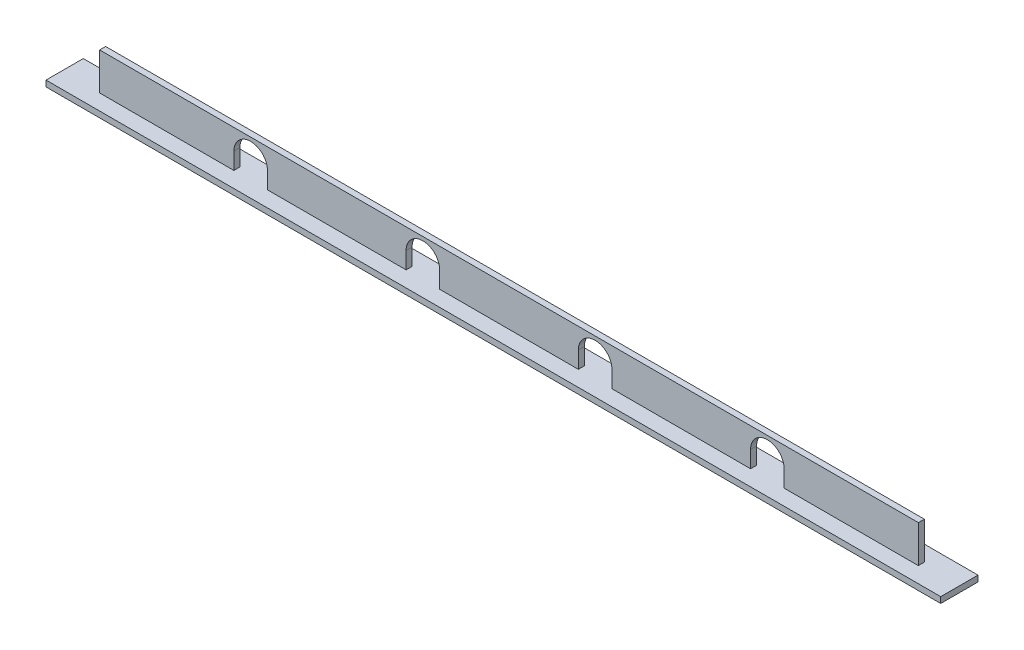
SolidWorks part; units mm, degrees
material "12Х18Н10Т ГОСТ 4543-71"
ref_plane "Спереди" through (0, 0, 0) normal (0, 0, 1) x (1, 0, 0)
ref_plane "Сверху" through (0, 0, 0) normal (0, 1, 0) x (1, 0, 0)
ref_plane "Справа" through (0, 0, 0) normal (1, 0, 0) x (0, 0, -1)
sketch "Эскиз1" plane through (0, 0, 0) normal (0, 0, 1) x (1, 0, 0)
  line L0 (-600, -2.5) -> (-600, -25)
  line L1 (-605, -25) -> (-600, -25)
  line L2 (-605, -25) -> (-605, 25)
  line L3 (-605, 25) -> (605, 25)
  line L4 (605, -25) -> (605, 25)
  line L5 (0, 25) -> (0, -25) construction
  line L6 (-605, 0) -> (605, 0) construction
  line L7 (-555, -2.5) -> (-555, -25)
  line L8 (-555, -25) -> (-369, -25)
  line L9 (-369, -2.5) -> (-369, -25)
  line L10 (-324, -2.5) -> (-324, -25)
  line L11 (-138, -2.5) -> (-138, -25)
  line L12 (-93, -2.5) -> (-93, -25)
  line L13 (93, -2.5) -> (93, -25)
  line L14 (138, -2.5) -> (138, -25)
  line L15 (324, -2.5) -> (324, -25)
  line L16 (369, -2.5) -> (369, -25)
  line L17 (555, -2.5) -> (555, -25)
  line L18 (600, -2.5) -> (600, -25)
  line L19 (-324, -25) -> (-138, -25)
  line L20 (-93, -25) -> (93, -25)
  line L21 (138, -25) -> (324, -25)
  line L22 (369, -25) -> (555, -25)
  line L23 (600, -25) -> (605, -25)
  arc A0 (-555, -2.5) -> (-600, -2.5) centre (-577.5, -2.5) ccw
  arc A1 (-324, -2.5) -> (-369, -2.5) centre (-346.5, -2.5) ccw
  arc A2 (-93, -2.5) -> (-138, -2.5) centre (-115.5, -2.5) ccw
  arc A3 (138, -2.5) -> (93, -2.5) centre (115.5, -2.5) ccw
  arc A4 (369, -2.5) -> (324, -2.5) centre (346.5, -2.5) ccw
  arc A5 (600, -2.5) -> (555, -2.5) centre (577.5, -2.5) ccw
  point P0 (0, 0)
  dimension "D3" = 45
  dimension "D1" = 1210
  dimension "D2" = 50
  dimension "D5" = 5
  dimension "D4" = 6
extrude "Бобышка-Вытянуть1" add sketch "Эскиз1" along normal mid plane 8
sketch "Эскиз3" plane through (0, 25, 0) normal (0, 1, 0) x (1, 0, 0)
  line L0 (0, -208.2618) -> (0, 258.9795) construction
  line L1 (555, -4) -> (555, 4) construction
  line L4 (605, 4) -> (-605, 4)
  line L5 (-605, 4) -> (-605, -4)
  line L6 (-605, -4) -> (605, -4)
  line L7 (605, -4) -> (605, 4)
  line L8 (549, 4) -> (-549, 4)
  line L9 (-549, 4) -> (-549, -4)
  line L10 (-549, -4) -> (549, -4)
  line L11 (549, -4) -> (549, 4)
  dimension "D2" = 6
  dimension "D1" = 0
extrude "Вырез-Вытянуть1" cut sketch "Эскиз3" against normal through all flip side to cut
sketch "Эскиз2" plane through (0, -25, 0) normal (0, -1, 0) x (1, 0, 0)
  line L1 (-600, -25) -> (600, -25)
  line L2 (-600, -25) -> (-600, 25)
  line L3 (-600, 25) -> (600, 25)
  line L4 (600, -25) -> (600, 25)
  line L5 (0, 25) -> (0, -25) construction
  line L6 (-600, 0) -> (600, 0) construction
  point P0 (0, 0)
  dimension "D1" = 50
  dimension "D2" = 1200
extrude "Бобышка-Вытянуть2" add sketch "Эскиз2" along normal blind 8 separate body
equation "\"расстояние между опорами фермы\"= 49"
equation "\"центр боковых направляющих\"= 1210 / 2"
equation "\"толщина полосы\"= 6"
equation "\"ширина полосы\"= 50"
equation "\"ширина боковой направляющей\"= 100 / 2"
equation "\"расстояние между центрами фиксатора\"= 178 / 2"
equation "\"D2@Эскиз3\"=\"толщина полосы\""
